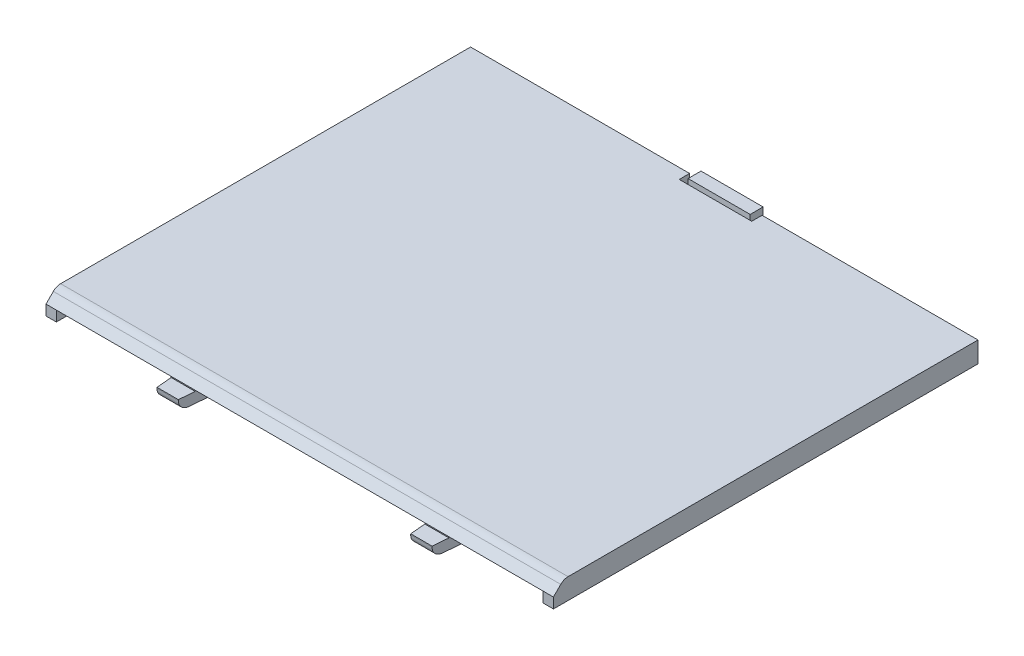
SolidWorks part; units mm, degrees
ref_plane "Front Plane" through (0, 0, 0) normal (0, 0, 1) x (1, 0, 0)
ref_plane "Top Plane" through (0, 0, 0) normal (0, 1, 0) x (1, 0, 0)
ref_plane "Right Plane" through (0, 0, 0) normal (1, 0, 0) x (0, 0, -1)
sketch "Sketch1" plane through (0, 0, 0) normal (0, 1, 0) x (1, 0, 0)
  line L1 (-49, 41) -> (49, 41)
  line L2 (-49, 41) -> (-49, -41)
  line L3 (-49, -41) -> (49, -41)
  line L4 (49, 41) -> (49, -41)
  line L5 (-49, 41) -> (49, -41) construction
  line L6 (-49, -41) -> (49, 41) construction
  point P0 (0, 0)
  dimension "D1" = 98
  dimension "D2" = 82
extrude "Boss-Extrude1" add sketch "Sketch1" along normal blind 2
sketch "Sketch2" plane through (0, 0, 0) normal (0, -1, 0) x (1, 0, 0)
  line L0 (49, -41) -> (-49, -41) construction
  line L1 (-49, 41) -> (-47, 41)
  line L2 (-49, 41) -> (-49, -41)
  line L3 (-49, -41) -> (-47, -41)
  line L4 (-47, 41) -> (-47, -41)
  line L6 (49, 41) -> (47, 41)
  line L7 (49, 41) -> (49, -41)
  line L8 (49, -41) -> (47, -41)
  line L9 (47, 41) -> (47, -41)
  dimension "D1" = 2
  dimension "D2" = 2
extrude "Boss-Extrude2" add sketch "Sketch2" along normal blind 2
chamfer "Chamfer1" distance 2 angle 45 1 edges at (0, 2, 41)
fillet "Fillet2" radius 2 1 edges at (0, 2, 39)
sketch "Sketch3" plane through (0, 0, 0) normal (0, -1, 0) x (1, 0, 0)
  line L0 (47, 41) -> (47, -41) construction
  line L1 (-47, 41) -> (47, 41)
  line L2 (-47, 41) -> (-47, 39)
  line L3 (-47, 39) -> (47, 39)
  line L4 (47, 41) -> (47, 39)
  dimension "D1" = 2
sketch "Sketch4" plane through (0, 0, 0) normal (0, -1, 0) x (1, 0, 0)
  line L0 (-47, 39) -> (47, 39) construction
  line L1 (-27, 39) -> (-22, 39)
  line L2 (-27, 39) -> (-27, 36)
  line L3 (-27, 36) -> (-22, 36)
  line L4 (-22, 39) -> (-22, 36)
  line L5 (-47, -41) -> (-47, 41) construction
  line L6 (0, 39) -> (0, 0) construction
  line L7 (27, 36) -> (22, 36)
  line L8 (22, 39) -> (22, 36)
  line L9 (27, 39) -> (22, 39)
  line L10 (27, 39) -> (27, 36)
  dimension "D1" = 20
  dimension "D2" = 5
  dimension "D3" = 3
extrude "Boss-Extrude4" add sketch "Sketch4" along normal blind 4.2
chamfer "Chamfer2" distance 4.2 angle 10 1 edges at (-24.5, -4.2, 36) first distance on face at (-24.5, -2.1, 36)
sketch "Sketch5" plane through (0, 0, 39) normal (0, 0, 1) x (1, 0, 0)
  line L0 (-22, -4.2) -> (-22, 0) construction
  line L1 (-27, -4.2) -> (-22, -4.2)
  line L2 (-27, -4.2) -> (-27, -2.2)
  line L3 (-27, -2.2) -> (-22, -2.2)
  line L4 (-22, -4.2) -> (-22, -2.2)
  dimension "D1" = 2
extrude "Boss-Extrude5" add sketch "Sketch5" along normal blind 3
chamfer "Chamfer5" distance 5 angle 5 2 edges at (-22, -3.2, 42) (-27, -3.2, 42) first distance on face at (-22, -2.1333, 39.1234) first distance on face at (-27, -2.1333, 39.1234)
fillet "Fillet3" radius 1.8 1 edges at (-24.5, -4.2, 42)
sketch "Sketch6" plane through (0, 0, 0) normal (0, -1, 0) x (1, 0, 0)
  line L0 (0, 41) -> (0, -43.0967) construction
  line L1 (-47, 41) -> (47, 41) construction
chamfer "Chamfer3" distance 4.2 angle 10 1 edges at (24.5, -4.2, 36) first distance on face at (24.5, -2.1, 36)
sketch "Sketch7" plane through (0, 0, 39) normal (0, 0, 1) x (1, 0, 0)
  line L0 (22, -4.2) -> (22, 0) construction
  line L1 (22, -2.2) -> (27, -2.2)
  line L2 (22, -2.2) -> (22, -4.2)
  line L3 (22, -4.2) -> (27, -4.2)
  line L4 (27, -2.2) -> (27, -4.2)
  dimension "D1" = 2
extrude "Boss-Extrude6" add sketch "Sketch7" along normal blind 3
chamfer "Chamfer4" distance 5 angle 5 2 edges at (22, -3.2, 42) (27, -3.2, 42) first distance on face at (22, -2.1333, 39.1234) first distance on face at (27, -2.1333, 39.1234)
fillet "Fillet4" radius 1.8 1 edges at (24.5, -4.2, 42)
sketch "Sketch8" plane through (0, 0, 0) normal (0, -1, 0) x (1, 0, 0)
  line L20 (0, 41) -> (0, -43.0967) construction
  line L21 (-6, -37.5) -> (6, -37.5)
  line L23 (-6, -37.5) -> (-6, -39)
  line L24 (-6, -39) -> (6, -39)
  line L25 (6, -37.5) -> (6, -39)
  line L26 (-6, -37.5) -> (6, -39) construction
  line L27 (-6, -39) -> (6, -37.5) construction
  line L28 (47, -41) -> (-47, -41) construction
  point P0 (0, -38.25)
  dimension "D1" = 1.5
  dimension "D2" = 12
  dimension "D3" = 2
sketch "Sketch13" plane through (0, 0, -41) normal (0, 0, -1) x (-1, 0, 0)
  line L0 (47, 0) -> (-47, 0) construction
  line L1 (-7.298, 2) -> (6.702, 2)
  line L2 (-7.298, 2) -> (-7.298, 0)
  line L3 (-7.298, 0) -> (6.702, 0)
  line L4 (6.702, 2) -> (6.702, 0)
  line L5 (-7.298, 2) -> (6.702, 0) construction
  line L6 (-7.298, 0) -> (6.702, 2) construction
  line L7 (-49, 2) -> (49, 2) construction
  point P0 (-0.298, 1)
  dimension "D1" = 0
  dimension "D2" = 14
extrude "Cut-Extrude1" cut sketch "Sketch13" against normal blind 2
ref_plane "Plane1" through (0, 0, 0) normal (1, 0, 0) x (0, 0, -1)
sketch "Sketch9" plane through (0, 0, 0) normal (1, 0, 0) x (0, 0, -1)
  line L0 (39, 0) -> (39, -4)
  line L1 (-41, 0) -> (43.0967, 0) construction
  line L2 (41, 2) -> (41, -2) construction
  line L3 (40, -4) -> (40, 2)
  line L4 (41, 2) -> (-38.1716, 2) construction
  arc A0 (39, -4) -> (40, -4) centre (39.5, -4) ccw
  dimension "D2" = 4
  dimension "D3" = 0.5
  dimension "D1" = 2
sweep "Sweep1" add profiles "Sketch8" path "Sketch9"
sketch "Sketch14" plane through (0, 0, -41.5) normal (0, 0, -1) x (-1, 0, 0)
  line L0 (6, -4) -> (6, 2) construction
  line L1 (-6, -4) -> (6, -4)
  line L2 (-6, -4) -> (-6, -1.5)
  line L3 (-6, -1.5) -> (6, -1.5)
  line L4 (6, -4) -> (6, -1.5)
  dimension "D1" = 2.5
extrude "Boss-Extrude10" add sketch "Sketch14" along normal blind 0.5
sketch "Sketch15" plane through (0, 0, -41.5) normal (0, 0, -1) x (-1, 0, 0)
  line L0 (6, -1.5) -> (6, 2) construction
  line L1 (-6, 2) -> (6, 2)
  line L2 (-6, 2) -> (-6, 0.1)
  line L3 (-6, 0.1) -> (6, 0.1)
  line L4 (6, 2) -> (6, 0.1)
  dimension "D1" = 1.9
extrude "Boss-Extrude11" add sketch "Sketch15" along normal blind 1
chamfer "Chamfer7" distance 2.5 angle 12 1 edges at (0, -4, -42) first distance on face at (0, -2.75, -42)
